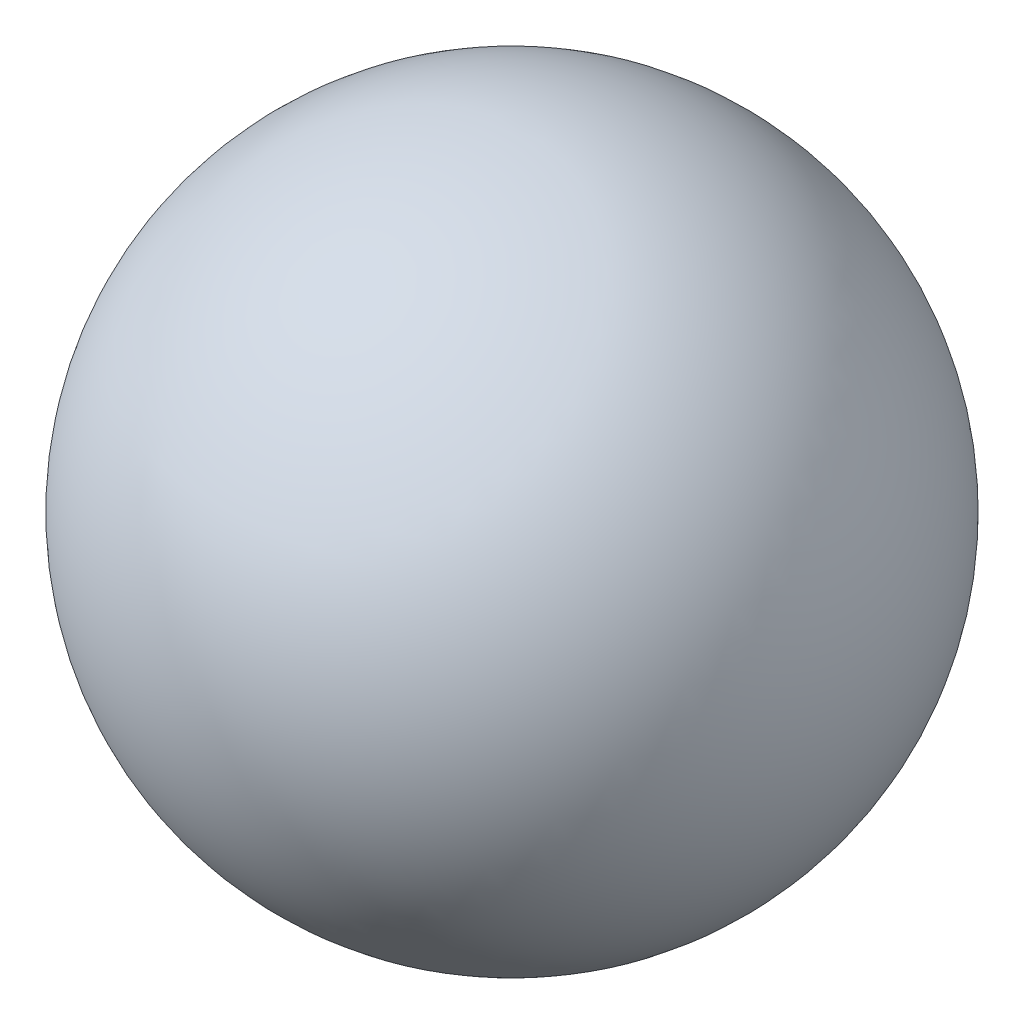
SolidWorks part; units mm, degrees
material "Custom Plastic"
ref_plane "Front Plane" through (0, 0, 0) normal (0, 0, 1) x (1, 0, 0)
ref_plane "Top Plane" through (0, 0, 0) normal (0, 1, 0) x (1, 0, 0)
ref_plane "Right Plane" through (0, 0, 0) normal (1, 0, 0) x (0, 0, -1)
sketch "Sketch1" plane through (0, 0, 0) normal (0, 0, 1) x (1, 0, 0)
  line L0 (0, -2.5146) -> (0, 2.5146) construction
  circle A0 centre (0, 0) radius 2.5146
  dimension "D1" = 5.0292
revolve "Revolve2" add sketch "Sketch1" angle 360 about L0 region at (-1.0672, 0, 0)
